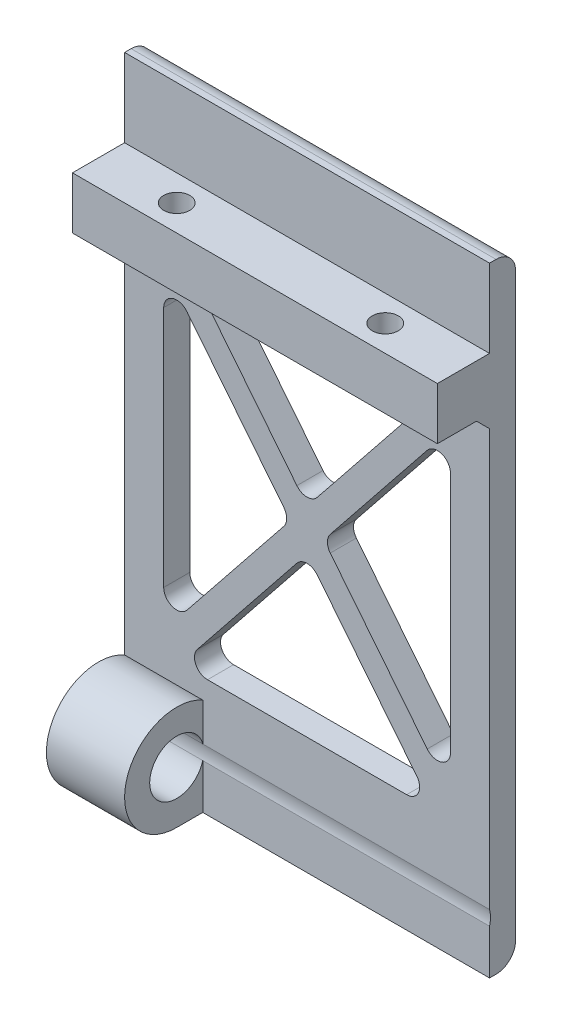
SolidWorks part; units mm, degrees
material "ABS"
ref_plane "前视基准面" through (0, 0, 0) normal (0, 0, 1) x (1, 0, 0)
ref_plane "上视基准面" through (0, 0, 0) normal (0, 1, 0) x (1, 0, 0)
ref_plane "右视基准面" through (0, 0, 0) normal (1, 0, 0) x (0, 0, -1)
other "Configuration Table"
sketch "草图1" plane through (0, 0, 0) normal (1, 0, 0) x (0, 0, -1)
  line L0 (-16.4301, -8) -> (8, -8)
  line L1 (8, -8) -> (8, 87)
  line L2 (8, 87) -> (4, 87)
  line L3 (4, 87) -> (4, 75)
  line L4 (4, 75) -> (-4, 75)
  line L5 (-4, 75) -> (-4, 67)
  line L6 (-4, 67) -> (4, 67)
  line L7 (4, 67) -> (4, 6.9282)
  circle A0 centre (0, 0) radius 4.15
  circle A1 centre (0, 0) radius 8
  dimension "D1" = 8.3
  dimension "D3" = 8
  dimension "D9" = 16
  dimension "D2" = 8
  dimension "D4" = 4
  dimension "D5" = 95
  dimension "D6" = 12
  dimension "D7" = 8
  dimension "D8" = 8
extrude "凸台-拉伸1" add sketch "草图1" along normal blind 56 contours A1 L1 L2 L3 L4 L5 L6 L7 | A1 A0 | A1 L0 L1 region at (0, -6.2131, -6.2131) region at (0, 2.012, 7.5088) region at (0, 50.029, -5.0393)
fillet "圆角1" radius 3 2 edges at (28, 87, -8) (28, -8, -8)
sketch "草图2" plane through (0, 0, 0) normal (-1, 0, 0) x (0, 0, 1)
  line L0 (-4, 6.9282) -> (-4, -8)
  line L1 (0, -8) -> (-5, -8) construction
  line L10 (-4, 87) -> (-5, 87)
  line L11 (-8, 84) -> (-8, -5)
  line L12 (-5, -8) -> (0, -8)
  line L13 (-4, 6.9282) -> (-4, 67)
  line L14 (-4, 67) -> (4, 67)
  line L15 (4, 67) -> (4, 75)
  line L16 (4, 75) -> (-4, 75)
  line L17 (-4, 75) -> (-4, 87)
  line L18 (-4, 87) -> (-5, 87)
  line L19 (-8, 84) -> (-8, -5)
  line L20 (-5, -8) -> (0, -8)
  line L21 (-4, 6.9282) -> (-4, 67)
  line L22 (-4, 67) -> (4, 67)
  line L23 (4, 67) -> (4, 75)
  line L24 (4, 75) -> (-4, 75)
  line L25 (-4, 75) -> (-4, 87)
  arc A4 (-5, 87) -> (-8, 84) centre (-5, 84) ccw
  arc A5 (-8, -5) -> (-5, -8) centre (-5, -5) ccw
  arc A6 (0, -8) -> (-4, 6.9282) centre (0, 0) ccw
  arc A7 (-5, 87) -> (-8, 84) centre (-5, 84) ccw
  arc A8 (-8, -5) -> (-5, -8) centre (-5, -5) ccw
  arc A9 (0, -8) -> (-4, 6.9282) centre (0, 0) ccw
  line M16 (-5, -8) -> (0, -8)
  arc M17 (0, -8) -> (-4, 6.9282) centre (0, 0) ccw
  circle M23 centre (0, 0) radius 4.15
  dimension "D1" = 0
extrude "切除-拉伸1" cut sketch "草图2" against normal blind 44 contours L0 M17 M23 M16 region at (0, 2.0188, 7.5342)
sketch "草图3" plane through (0, 0, -4) normal (0, 0, 1) x (1, 0, 0)
  line L0 (44, 8) -> (0, 8) construction
  line L1 (14.1436, 57.5) -> (22.5889, 42.8724)
  line L2 (0, 67) -> (0, 1.1057) construction
  line L3 (28, 67) -> (28, 8) construction
  line L4 (56, 67) -> (0, 67) construction
  line L5 (15.8756, 58.5) -> (22.8038, 46.5) construction
  line L6 (38.3923, 37.5) -> (33.1962, 46.5)
  line L7 (33.1962, 46.5) -> (22.8038, 46.5)
  line L8 (22.8038, 46.5) -> (17.6077, 37.5)
  line L9 (17.6077, 37.5) -> (22.8038, 28.5)
  line L10 (22.8038, 28.5) -> (33.1962, 28.5)
  line L11 (33.1962, 28.5) -> (38.3923, 37.5)
  line L12 (52.2487, 37.5) -> (40.1244, 58.5)
  line L13 (40.1244, 58.5) -> (15.8756, 58.5)
  line L14 (15.8756, 58.5) -> (3.7513, 37.5)
  line L15 (3.7513, 37.5) -> (15.8756, 16.5)
  line L16 (15.8756, 16.5) -> (40.1244, 16.5)
  line L17 (40.1244, 16.5) -> (52.2487, 37.5)
  line L18 (40.1244, 58.5) -> (33.1962, 46.5) construction
  line L19 (38.3923, 37.5) -> (52.2487, 37.5) construction
  line L20 (33.1962, 28.5) -> (40.1244, 16.5) construction
  line L21 (22.8038, 28.5) -> (15.8756, 16.5) construction
  line L22 (17.6077, 37.5) -> (3.7513, 37.5) construction
  line L23 (38.3923, 59.5) -> (30.1226, 45.1764)
  line L24 (34.9282, 37.5) -> (31.4641, 43.5)
  line L25 (31.4641, 43.5) -> (24.5359, 43.5)
  line L26 (24.5359, 43.5) -> (21.0718, 37.5)
  line L27 (21.0718, 37.5) -> (24.5359, 31.5)
  line L28 (24.5359, 31.5) -> (31.4641, 31.5)
  line L29 (31.4641, 31.5) -> (34.9282, 37.5)
  line L30 (21.0718, 39.5) -> (3.7513, 39.5)
  line L31 (22.2269, 31.5006) -> (14.1436, 17.5)
  line L32 (30.1194, 29.8291) -> (38.3923, 15.5)
  line L33 (35.2754, 35.5) -> (52.2487, 35.5)
  line L34 (17.6077, 59.5) -> (25.8849, 45.1634)
  line L35 (41.8564, 57.5) -> (33.7653, 43.4858)
  line L36 (20.7056, 35.5) -> (3.7513, 35.5)
  line L37 (26.2297, 30.4338) -> (17.6077, 15.5)
  line L38 (33.7715, 31.5035) -> (41.8564, 17.5)
  line L39 (35.7942, 39.5) -> (52.2487, 39.5)
  line L40 (14.1436, 57.5) -> (21.0718, 45.5) construction
  line L41 (17.6077, 59.5) -> (24.5359, 47.5) construction
  line L42 (38.3923, 59.5) -> (31.4641, 47.5) construction
  line L43 (41.8564, 57.5) -> (34.9282, 45.5) construction
  line L44 (38.3923, 39.5) -> (52.2487, 39.5) construction
  line L45 (38.3923, 35.5) -> (52.2487, 35.5) construction
  line L46 (34.9282, 29.5) -> (41.8564, 17.5) construction
  line L47 (31.4641, 27.5) -> (38.3923, 15.5) construction
  line L48 (24.5359, 27.5) -> (17.6077, 15.5) construction
  line L49 (21.0718, 29.5) -> (14.1436, 17.5) construction
  line L50 (17.6077, 35.5) -> (3.7513, 35.5) construction
  line L51 (17.6077, 39.5) -> (3.7513, 39.5) construction
  circle A0 centre (28, 37.5) radius 9 construction
  circle A1 centre (28, 37.5) radius 21 construction
  circle A2 centre (28, 37.5) radius 6 construction
  dimension "D1" = 18
  dimension "D3" = 12
  dimension "D4" = 2
  dimension "D5" = 2
extrude "切除-拉伸2" [suppressed] cut sketch "草图3" against normal blind 40 contours L13 L34 L7 L23 | L6 L39 L12 L35 | L11 L38 L17 L33 | L10 L37 L16 L32 | L9 L36 L15 L31 | L30 L8 L1 L14 | L28 L29 L24 L25 L26 L27
fillet "圆角2" [suppressed] radius 1
sketch "草图4" plane through (0, 0, -4) normal (0, 0, 1) x (1, 0, 0)
  line L0 (44, 8) -> (0, 8) construction
  line L1 (0, 67) -> (0, 1.1057) construction
  line L2 (28, 67) -> (28, 8) construction
  line L3 (56, 67) -> (0, 67) construction
  line L4 (51.5617, 11.2494) -> (7.5617, 66.2494)
  line L5 (50, 10) -> (6, 10)
  line L6 (50, 10) -> (50, 65)
  line L7 (50, 65) -> (6, 65)
  line L8 (6, 10) -> (6, 65)
  line L9 (50, 10) -> (6, 65) construction
  line L10 (50, 65) -> (6, 10) construction
  line L11 (48.4383, 66.2494) -> (4.4383, 11.2494)
  line L12 (48.4383, 8.7506) -> (4.4383, 63.7506)
  line L13 (51.5617, 63.7506) -> (7.5617, 8.7506)
  point P9 (28, 37.5)
  dimension "D1" = 2
  dimension "D2" = 6
  dimension "D3" = 2
  dimension "D4" = 2
extrude "切除-拉伸3" cut sketch "草图4" against normal blind 40 contours L11 L7 L4 | L11 L12 L8 | L12 L13 L5 | L6 L13 L4 region at (43.5204, 37.5, -4) region at (28, 56.9005, -4) region at (28, 18.0995, -4) region at (12.4796, 37.5, -4)
fillet "圆角3" radius 2 12 edges at (6, 13.2016, -6) (6, 61.7984, -6) (25.4388, 37.5, -6) (50, 61.7984, -6) (50, 13.2016, -6) (28, 40.7016, -6) (8.5612, 65, -6) (47.4388, 65, -6) (8.5612, 10, -6) (28, 34.2984, -6) (47.4388, 10, -6) (30.5612, 37.5, -6)
sketch "草图5" plane through (0, 67, 0) normal (0, -1, 0) x (1, 0, 0)
  arc A4 (4, -2) -> (4, 2) centre (4, 0) ccw construction
  arc A5 (4, 2) -> (4, -2) centre (4, 0) ccw construction
  arc A8 (52, -2) -> (52, 2) centre (52, 0) ccw construction
  arc A9 (52, 2) -> (52, -2) centre (52, 0) ccw construction
  arc A12 (44, -2) -> (44, 2) centre (44, 0) ccw
  arc A13 (44, 2) -> (44, -2) centre (44, 0) ccw
  arc A16 (12, -2) -> (12, 2) centre (12, 0) ccw
  arc A17 (12, 2) -> (12, -2) centre (12, 0) ccw
  arc A20 (20, -2) -> (20, 2) centre (20, 0) ccw construction
  arc A21 (20, 2) -> (20, -2) centre (20, 0) ccw construction
  arc A24 (28, -2) -> (28, 2) centre (28, 0) ccw construction
  arc A25 (28, 2) -> (28, -2) centre (28, 0) ccw construction
  arc A28 (36, -2) -> (36, 2) centre (36, 0) ccw construction
  arc A29 (36, 2) -> (36, -2) centre (36, 0) ccw construction
extrude "切除-拉伸4" cut sketch "草图5" against normal blind 40
sketch "草图6" plane through (0, 67, 0) normal (0, -1, 0) x (1, 0, 0)
  line L1 (16.1858, 0) -> (14.0929, 3.625)
  line L2 (14.0929, 3.625) -> (9.9071, 3.625)
  line L3 (9.9071, 3.625) -> (7.8142, 0)
  line L4 (7.8142, 0) -> (9.9071, -3.625)
  line L5 (9.9071, -3.625) -> (14.0929, -3.625)
  line L6 (14.0929, -3.625) -> (16.1858, 0)
  line L7 (39.8142, 0) -> (41.9071, -3.625)
  line L8 (41.9071, -3.625) -> (46.0929, -3.625)
  line L9 (46.0929, -3.625) -> (48.1858, 0)
  line L10 (48.1858, 0) -> (46.0929, 3.625)
  line L11 (46.0929, 3.625) -> (41.9071, 3.625)
  line L12 (41.9071, 3.625) -> (39.8142, 0)
  circle A0 centre (12, 0) radius 3.625 construction
  circle A1 centre (44, 0) radius 3.625 construction
  dimension "D1" = 7.25
extrude "切除-拉伸5" cut sketch "草图6" against normal blind 4
fillet "圆角4" radius 0.5 12 edges at (41.9071, 69, -3.625) (46.0929, 69, -3.625) (48.1858, 69, 0) (46.0929, 69, 3.625) (41.9071, 69, 3.625) (39.8142, 69, 0) (14.0929, 69, 3.625) (9.9071, 69, 3.625) (7.8142, 69, 0) (9.9071, 69, -3.625) (16.1858, 69, 0) (14.0929, 69, -3.625)
chamfer "倒角1" distance 2 angle 45 1 edges at (28, 67, -4)
sketch "草图7" plane through (0, 0, 0) normal (-1, 0, 0) x (0, 0, 1)
  line L3 (-4, 6.9282) -> (-4, 1.1057)
  line L4 (-4, -1.1057) -> (-4, -8)
  line L5 (-4, -8) -> (0, -8)
  line L6 (-4, 6.9282) -> (-4, 1.1057)
  line L7 (-4, -1.1057) -> (-4, -8)
  line L8 (-4, -8) -> (0, -8)
  arc A2 (0, -8) -> (-4, 6.9282) centre (0, 0) ccw
  arc A3 (-4, -1.1057) -> (-4, 1.1057) centre (0, 0) ccw
  arc A4 (0, -8) -> (-4, 6.9282) centre (0, 0) ccw
  arc A5 (-4, -1.1057) -> (-4, 1.1057) centre (0, 0) ccw
  dimension "D1" = 0
extrude "凸台-拉伸2" add sketch "草图7" against normal blind 12 separate body
sketch "草图8" plane through (44, 0, 0) normal (-1, 0, 0) x (0, 0, 1)
  line L3 (-4, 6.9282) -> (-4, 1.1057)
  line L4 (-4, -1.1057) -> (-4, -8)
  line L5 (-4, -8) -> (0, -8)
  line L6 (-4, 6.9282) -> (-4, 1.1057)
  line L7 (-4, -1.1057) -> (-4, -8)
  line L8 (-4, -8) -> (0, -8)
  arc A2 (0, -8) -> (-4, 6.9282) centre (0, 0) ccw
  arc A3 (-4, -1.1057) -> (-4, 1.1057) centre (0, 0) ccw
  arc A4 (0, -8) -> (-4, 6.9282) centre (0, 0) ccw
  arc A5 (-4, -1.1057) -> (-4, 1.1057) centre (0, 0) ccw
  dimension "D1" = 0
extrude "切除-拉伸6" cut sketch "草图8" against normal blind 12
